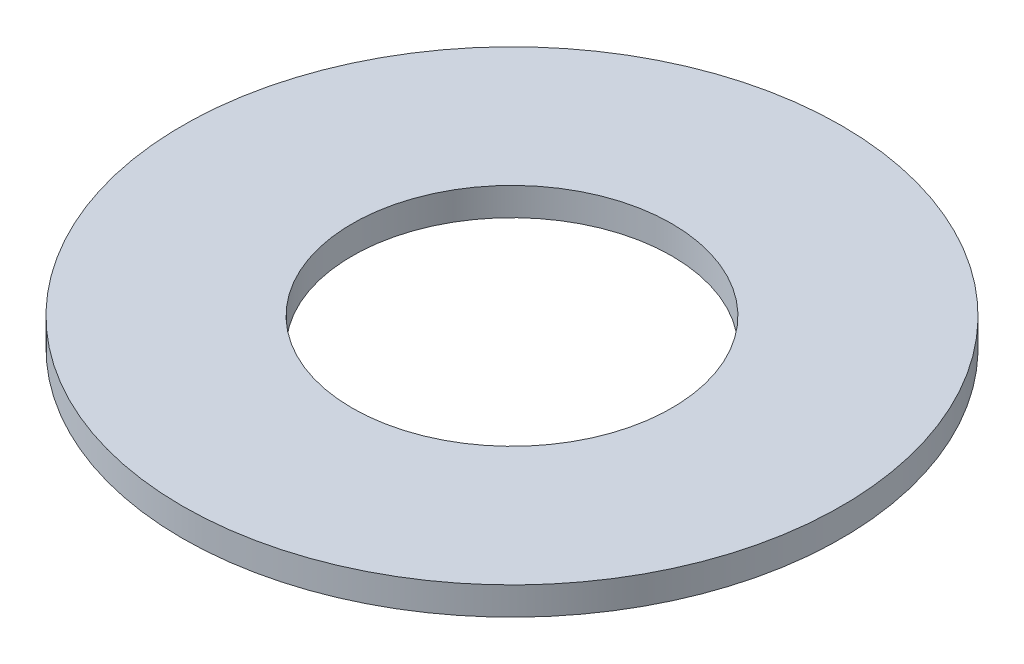
SolidWorks part; units mm, degrees
ref_plane "Front Plane" through (0, 0, 0) normal (0, 0, 1) x (1, 0, 0)
ref_plane "Top Plane" through (0, 0, 0) normal (0, 1, 0) x (1, 0, 0)
ref_plane "Right Plane" through (0, 0, 0) normal (1, 0, 0) x (0, 0, -1)
sketch "Sketch1" plane through (0, 0, 0) normal (0, 1, 0) x (1, 0, 0)
  circle A0 centre (0, 0) radius 82.5
  dimension "FLANGE_OD" = 165
extrude "Boss-Extrude1" add sketch "Sketch1" along normal blind 7
sketch "Sketch2" plane through (0, 0, 0) normal (0, 1, 0) x (1, 0, 0)
  circle A0 centre (0, 0) radius 40
  dimension "BORE_D" = 80
extrude "Cut-Extrude1" cut sketch "Sketch2" along normal through all
sketch "Sketch3" plane through (0, 7, 0) normal (0, 1, 0) x (1, 0, 0)
  circle A0 centre (0, 0) radius 33.0948 construction
  circle A1 centre (-33.0948, 0) radius 3.7105
  dimension "BOLT_D" = 7.4209
  dimension "BOLT_PCD" = 66.1897
extrude "Cut-Extrude2" cut sketch "Sketch3" against normal blind 5.6522 rebuild error yes
pattern_circular "CirPattern1" count 4 over 360 rebuild error yes
